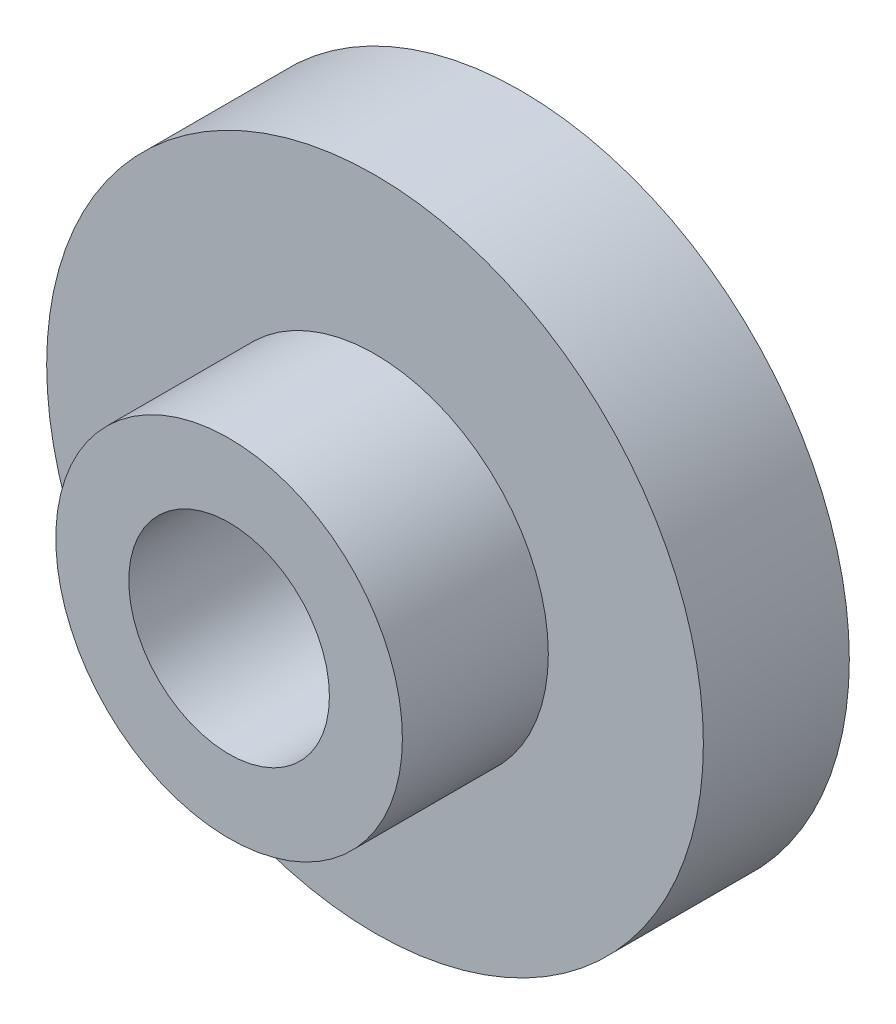
SolidWorks part; units mm, degrees
ref_plane "Front Plane" through (0, 0, 0) normal (0, 0, 1) x (1, 0, 0)
ref_plane "Top Plane" through (0, 0, 0) normal (0, 1, 0) x (1, 0, 0)
ref_plane "Right Plane" through (0, 0, 0) normal (1, 0, 0) x (0, 0, -1)
sketch "Sketch3" plane through (0, 0, 0) normal (0, 0, 1) x (1, 0, 0)
  circle A0 centre (0, 0) radius 1.375
  circle A1 centre (0, 0) radius 2.375
  circle A2 centre (0, 0) radius 4.5
  dimension "D1" = 2.75
  dimension "D2" = 4.75
  dimension "D3" = 9
extrude "Boss-Extrude1" add sketch "Sketch3" along normal blind 4 contours A1 A0 region at (-2.3078, 0, 0)
extrude "Boss-Extrude2" add sketch "Sketch3<3>" along normal blind 2 contours A2 A1 region at (-4.3727, 0, 0)
sketch "Sketch3<3>" plane through (0, 0, 0) normal (0, 0, 1) x (1, 0, 0) same geometry as "Sketch3"
